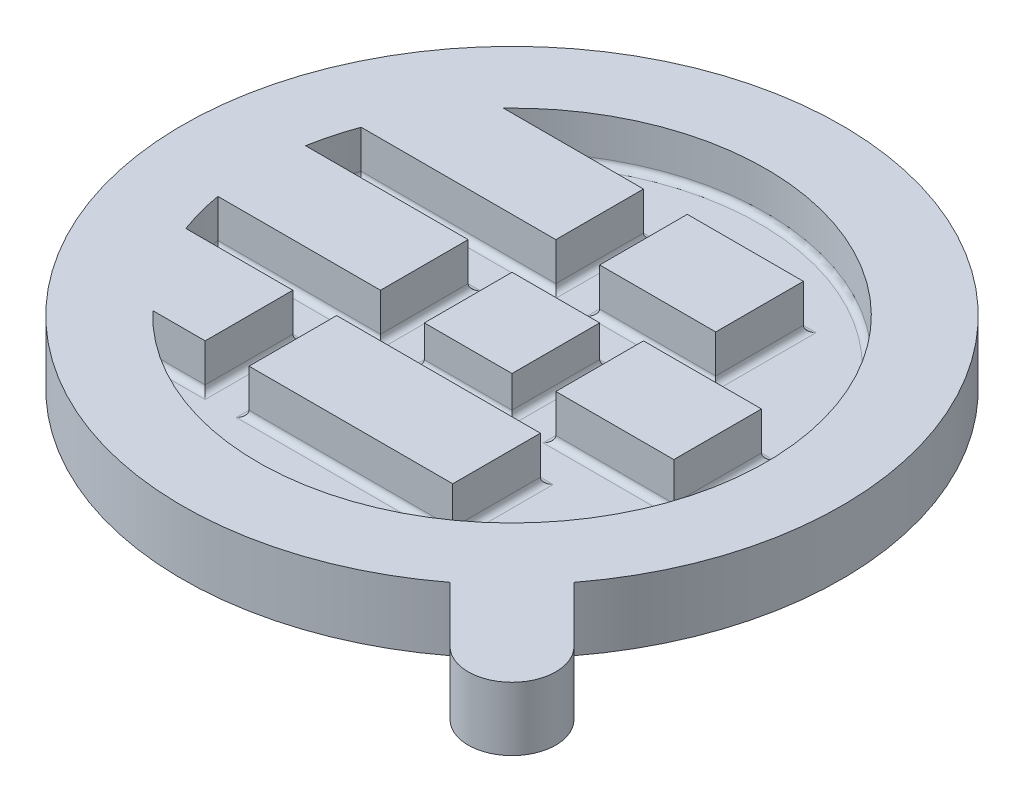
SolidWorks part; units mm, degrees
ref_plane "Front Plane" through (0, 0, 0) normal (0, 0, 1) x (1, 0, 0)
ref_plane "Top Plane" through (0, 0, 0) normal (0, 1, 0) x (1, 0, 0)
ref_plane "Right Plane" through (0, 0, 0) normal (1, 0, 0) x (0, 0, -1)
sketch "Sketch1" plane through (0, 0, 0) normal (0, 1, 0) x (1, 0, 0)
  line L0 (100, 100) -> (0, 0) construction
  line L1 (0, 0) -> (100, 0) construction
  line L2 (0, 0) -> (0, 100) construction
  line L3 (0, 100) -> (100, 100) construction
  line L5 (0, 100) -> (100, 0) construction
  line L6 (100, 9.7581) -> (78.7868, 30.9713)
  line L7 (90.2419, 0) -> (69.0287, 21.2132)
  line L8 (100, 9.7581) -> (90.2419, 0)
  line L9 (78.7868, 30.9713) -> (69.0287, 21.2132) construction
  line L10 (50, 50) -> (0, 50) construction
  line L11 (43.1, 56.9) -> (56.9, 56.9)
  line L12 (43.1, 56.9) -> (43.1, 43.1)
  line L13 (43.1, 43.1) -> (56.9, 43.1)
  line L14 (56.9, 56.9) -> (56.9, 43.1)
  line L15 (43.1, 56.9) -> (56.9, 43.1) construction
  line L16 (43.1, 43.1) -> (56.9, 56.9) construction
  line L17 (70.7, 29.3) -> (0, 29.3) construction
  line L18 (10, 56.9) -> (36.2, 56.9)
  line L19 (10, 56.9) -> (10, 43.1)
  line L20 (10, 43.1) -> (36.2, 43.1)
  line L21 (36.2, 56.9) -> (36.2, 43.1)
  line L22 (10, 56.9) -> (36.2, 43.1) construction
  line L23 (10, 43.1) -> (36.2, 56.9) construction
  line L24 (70.7, 70.7) -> (0, 70.7) construction
  line L25 (50, 50) -> (50, 100) construction
  line L26 (12.4559, 77.6) -> (43.1, 77.6)
  line L27 (12.4559, 77.6) -> (12.4559, 63.8)
  line L28 (12.4559, 63.8) -> (43.1, 63.8)
  line L29 (43.1, 77.6) -> (43.1, 63.8)
  line L30 (12.4559, 77.6) -> (43.1, 63.8) construction
  line L31 (12.4559, 63.8) -> (43.1, 77.6) construction
  line L32 (50, 50) -> (100, 50) construction
  line L33 (50, 77.6) -> (68.27, 77.6)
  line L34 (50, 77.6) -> (50, 63.8)
  line L35 (50, 63.8) -> (68.27, 63.8)
  line L36 (68.27, 77.6) -> (68.27, 63.8)
  line L37 (50, 77.6) -> (68.27, 63.8) construction
  line L38 (50, 63.8) -> (68.27, 77.6) construction
  line L40 (63.8, 56.9) -> (82.37, 56.9)
  line L41 (63.8, 56.9) -> (63.8, 43.1)
  line L42 (63.8, 43.1) -> (82.37, 43.1)
  line L43 (82.37, 56.9) -> (82.37, 43.1)
  line L44 (63.8, 56.9) -> (82.37, 43.1) construction
  line L45 (63.8, 43.1) -> (82.37, 56.9) construction
  line L46 (12.4559, 36.2) -> (29.3, 36.2)
  line L47 (12.4559, 36.2) -> (12.4559, 22.4)
  line L48 (12.4559, 22.4) -> (29.3, 22.4)
  line L49 (29.3, 36.2) -> (29.3, 22.4)
  line L50 (12.4559, 36.2) -> (29.3, 22.4) construction
  line L51 (12.4559, 22.4) -> (29.3, 36.2) construction
  line L52 (36.2, 36.2) -> (68.27, 36.2)
  line L53 (36.2, 36.2) -> (36.2, 22.4)
  line L54 (36.2, 22.4) -> (68.27, 22.4)
  line L55 (68.27, 36.2) -> (68.27, 22.4)
  line L56 (36.2, 36.2) -> (68.27, 22.4) construction
  line L57 (36.2, 22.4) -> (68.27, 36.2) construction
  circle A0 centre (50, 50) radius 50
  arc A1 (100, 9.7581) -> (90.2419, 0) centre (95.121, 4.879) cw
  circle A2 centre (50, 50) radius 40
  circle A3 centre (68.27, 77.6) radius 6.9009 construction
  circle A4 centre (82.37, 56.9) radius 6.9028 construction
  circle A5 centre (68.27, 22.4) radius 6.9009 construction
  circle A6 centre (50, 50) radius 51.9
  point P19 (23.1, 50)
  point P29 (27.7779, 70.7)
  point P34 (59.135, 70.7)
  point P40 (73.085, 50)
  point P46 (20.8779, 29.3)
  point P52 (52.235, 29.3)
  dimension "D5" = 30
  dimension "D12" = 20.7
  dimension "D24" = 6.9009
  dimension "D25" = 6.9028
  dimension "D27" = 11.9
  dimension "D1" = 100
  dimension "D2" = 100
  dimension "D3" = 6.9
  dimension "D4" = 6.9
  dimension "D7" = 13.8
  dimension "D8" = 13.8
  dimension "D9" = 13.8
  dimension "D10" = 26.2
  dimension "D11" = 6.9
  dimension "D13" = 20.7
  dimension "D14" = 13.8
  dimension "D15" = 13.8
  dimension "D16" = 18.27
  dimension "D17" = 6.9
  dimension "D18" = 13.8
  dimension "D19" = 6.9
  dimension "D20" = 18.57
  dimension "D21" = 13.8
  dimension "D22" = 6.9
  dimension "D23" = 13.8
  dimension "D26" = 6.9009
  dimension "D6" = 10
extrude "Boss-Extrude12" add sketch "Sketch1" along normal blind 3 contours A2 L18 L19 | A2 L19 L20 | A2 L27 L26 L6 A0 L7 L48 L47 L20 L19 L18 | A2 L26 L27 | L18 A2 L20 L21 | L46 A2 L48 L49 | A2 L47 L48 | L26 A2 L28 L29 | L36 L33 L34 L35 | L43 L40 L41 L42 | L14 L11 L12 L13 | L55 L52 L53 L54 | A2 L7 A0 L6 | A0 L7 L8 L6 | A1 L8 | L28 A2 L18 L21 L20 L46 L49 L48 L26 L29 L52 L55 L54 L53 L40 L43 L42 L41 L33 L36 L35 L34 L11 L14 L13 L12 | L6 A6 L7 A0 | L7 A6 L6 A0 region at (90.8552, 0, -9.1448) region at (97.1917, 0, -2.8083) region at (85.9163, 0, -14.0837) region at (91.6121, 0, -20.222) region at (81.6927, 0, -18.3073) region at (87.3177, 0, -24.4404) region at (77.4873, 0, -22.5127) region at (22.4668, 0, -30.0395) region at (15.1126, 0, -26.6168) region at (15.1126, 0, -73.3832) region at (29.4847, 0, -70.3384) region at (23.199, 0, -50) region at (10.1797, 0, -44.8224) region at (10.1797, 0, -55.1776) region at (50, 0, -50) region at (59.135, 0, -70.7) region at (73.085, 0, -50) region at (52.235, 0, -29.3)
extrude "Boss-Extrude13" add sketch "Sketch1<16>" along normal blind 10 contours A2 L27 L26 L6 A0 L7 L48 L47 L20 L19 L18 | A2 L26 L27 | A2 L18 L19 | A2 L19 L20 | L18 A2 L20 L21 | L26 A2 L28 L29 | L36 L33 L34 L35 | L46 A2 L48 L49 | A2 L47 L48 | L55 L52 L53 L54 | L43 L40 L41 L42 | A2 L7 A0 L6 | A0 L7 L8 L6 | A1 L8 | L6 A6 L7 A0 | L7 A6 L6 A0 region at (90.8552, 0, -9.1448) region at (97.1917, 0, -2.8083) region at (85.9163, 0, -14.0837) region at (91.6121, 0, -20.222) region at (81.6927, 0, -18.3073) region at (87.3177, 0, -24.4404) region at (22.4668, 0, -30.0395) region at (15.1126, 0, -26.6168) region at (15.1126, 0, -73.3832) region at (29.4847, 0, -70.3384) region at (23.199, 0, -50) region at (10.1797, 0, -44.8224) region at (10.1797, 0, -55.1776) region at (59.135, 0, -70.7) region at (73.085, 0, -50) region at (52.235, 0, -29.3)
sketch "Sketch1<16>" plane through (0, 0, 0) normal (0, 1, 0) x (1, 0, 0) same geometry as "Sketch1"
extrude "Boss-Extrude14" add sketch "Sketch1<17>" along normal blind 9 contours L11 L14 L13 L12
sketch "Sketch1<17>" plane through (0, 0, 0) normal (0, 1, 0) x (1, 0, 0) same geometry as "Sketch1"
fillet "Fillet1" radius 1 28 edges at (90, 3, -50) (36.2, 3, -29.3) (52.235, 3, -22.4) (50, 3, -70.7) (59.135, 3, -63.8) (43.1, 3, -50) (50, 3, -43.1) (63.8, 3, -50) (73.085, 3, -43.1) (50, 3, -56.9) (73.085, 3, -56.9) (56.9, 3, -50) (52.235, 3, -36.2) (68.27, 3, -29.3) (82.37, 3, -50) (68.27, 3, -70.7) (59.135, 3, -77.6) (32.0738, 3, -77.6) (43.1, 3, -70.7) (27.7779, 3, -63.8) (11.3734, 3, -60.3915) (23.3998, 3, -56.9) (36.2, 3, -50) (23.3998, 3, -43.1) (11.3734, 3, -39.6085) (20.8779, 3, -36.2) (29.3, 3, -29.3) (25.1738, 3, -22.4)
